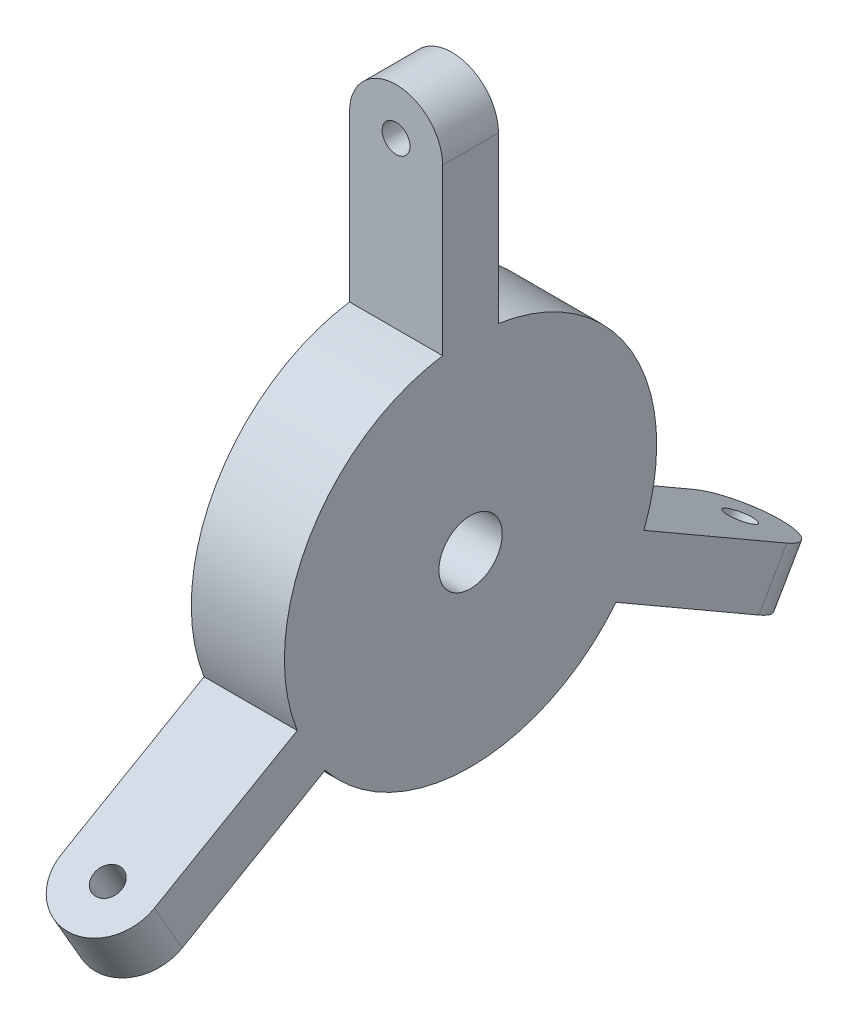
SolidWorks part; units mm, degrees
ref_plane "Plan de face" through (0, 0, 0) normal (0, 0, 1) x (1, 0, 0)
ref_plane "Plan de dessus" through (0, 0, 0) normal (0, 1, 0) x (1, 0, 0)
ref_plane "Plan de droite" through (0, 0, 0) normal (1, 0, 0) x (0, 0, -1)
sketch "Esquisse1" plane through (0, 0, 0) normal (1, 0, 0) x (0, 0, -1)
  line L0 (0, 0) -> (0, 42.5) construction
  line L1 (-3, 42.5) -> (3, 42.5)
  line L2 (-3, 42.5) -> (-3, 19.7737)
  line L3 (3, 42.5) -> (3, 19.7737)
  line L4 (38.3061, -18.6519) -> (18.6245, -7.2888)
  line L5 (38.3061, -18.6519) -> (35.3061, -23.8481)
  line L6 (35.3061, -23.8481) -> (15.6245, -12.4849)
  line L7 (-35.3061, -23.8481) -> (-15.6245, -12.4849)
  line L8 (-35.3061, -23.8481) -> (-38.3061, -18.6519)
  line L9 (-38.3061, -18.6519) -> (-18.6245, -7.2888)
  arc A0 (3, 19.7737) -> (18.6245, -7.2888) centre (0, 0) cw
  arc A1 (15.6245, -12.4849) -> (-15.6245, -12.4849) centre (0, 0) cw
  arc A2 (-18.6245, -7.2888) -> (-3, 19.7737) centre (0, 0) cw
  circle A3 centre (0, 0) radius 20 construction
  point P21 (0, 0)
  dimension "D4" = 20
  dimension "D1" = 42.5
  dimension "D2" = 6
  dimension "D3" = 3
extrude "Boss.-Extru.1" add sketch "Esquisse1" along normal blind 5 and the other way blind 5
hole_wizard "Trou taraudé M81" positions "Esquisse3" profile "Esquisse4" tap size "M8" standard "ISO" end condition through all
sketch "Esquisse3" plane through (5, 0, 0) normal (1, 0, 0) x (0, 0, -1)
  point P0 (0, 0)
sketch "Esquisse4" plane through (5, 0, 0) normal (0, 1, 0) x (0, 0, -1)
  line L0 (0, 0) -> (0, 10)
  line L1 (0, 10) -> (3.4, 10)
  line L2 (3.4, 10) -> (3.4, 0)
  line L5 (3.4, 0) -> (0, 0)
  line L11 (0, -6.35) -> (0, 107.95) construction
  dimension "Diamètre du trou pour taraudage jusqu'au prochain" = 6.8
  dimension "Profondeur du trou pour taraudage jusqu'au prochain" = 10
cosmetic thread "Filetage de perçage1" parameters "D2"=8
sketch "Esquisse5" plane through (0, 0, 3) normal (0, 0, 1) x (1, 0, 0)
  line L0 (0, 42.5) -> (0, 0) construction
  line L2 (-5, 19.7737) -> (-5, 37.5)
  line L3 (-5, 42.5) -> (-5, 19.7737) construction
  line L4 (-5, 19.7737) -> (-13.1992, 19.7737)
  line L5 (-13.1992, 19.7737) -> (-13.1992, 47.5)
  line L6 (-13.1992, 47.5) -> (13.6203, 47.5)
  line L7 (13.6203, 47.5) -> (13.6203, 19.7737)
  line L8 (13.6203, 19.7737) -> (5, 19.7737)
  line L9 (5, 19.7737) -> (5, 37.5)
  line L10 (5, 42.5) -> (5, 19.7737) construction
  line L11 (-5, 42.5) -> (5, 42.5) construction
  arc A1 (-5, 37.5) -> (5, 37.5) centre (0, 37.5) cw
  circle A2 centre (0, 37.5) radius 1.5
  dimension "D1" = 3
  dimension "D5" = 5
  dimension "D2" = 8.1992
  dimension "D3" = 8.6203
  dimension "D4" = 5
extrude "Enlèv. mat.-Extru.1" cut sketch "Esquisse5" against normal through all
pattern_circular "Répétition circulaire1" count 3 over 360 about axis through (5, 0, 0) along (1, 0, 0) of "Enlèv. mat.-Extru.1"
